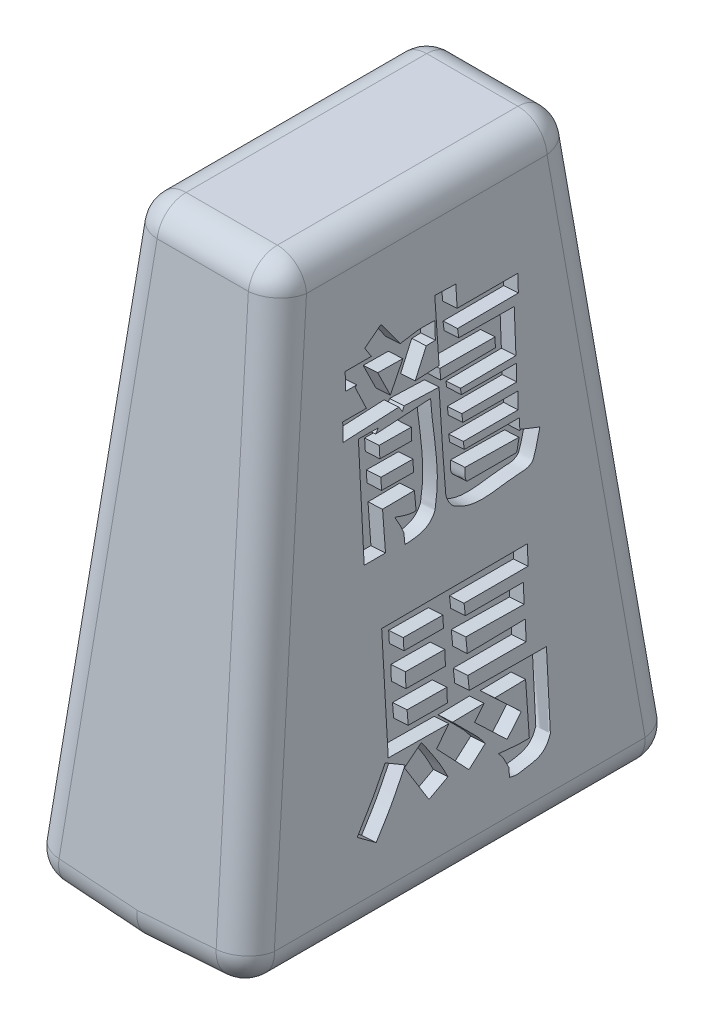
SolidWorks part; units mm, degrees
ref_plane "Płaszczyzna przednia" through (0, 0, 0) normal (0, 0, 1) x (1, 0, 0)
ref_plane "Płaszczyzna górna" through (0, 0, 0) normal (0, 1, 0) x (1, 0, 0)
ref_plane "Płaszczyzna prawa" through (0, 0, 0) normal (1, 0, 0) x (0, 0, -1)
sketch "Szkic1" plane through (0, 0, 0) normal (0, 0, 1) x (1, 0, 0)
  line L0 (0, 0) -> (0, 40)
  line L1 (3.1225, 40) -> (-3.1225, 40)
  line L2 (-5.1185, 38.1262) -> (-7.3738, 2.4704)
  line L3 (-5.504, 0.3481) -> (0, 0)
  line L4 (5.504, 0.3481) -> (0, 0)
  line L5 (5.1185, 38.1262) -> (7.3738, 2.4704)
  arc A0 (-3.1225, 40) -> (-5.1185, 38.1262) centre (-3.1225, 38) ccw
  arc A1 (-7.3738, 2.4704) -> (-5.504, 0.3481) centre (-5.3777, 2.3441) ccw
  arc A2 (7.3738, 2.4704) -> (5.504, 0.3481) centre (5.3777, 2.3441) cw
  arc A3 (3.1225, 40) -> (5.1185, 38.1262) centre (3.1225, 38) cw
  point P7 (-5, 40)
  point P10 (-7.5, 0.4744)
  point P17 (7.5, 0.4744)
  point P18 (5, 40)
  dimension "D5" = 2
  dimension "D1" = 40
  dimension "D2" = 90
  dimension "D3" = 5
  dimension "D4" = 7.5
extrude "Dodanie-wyciągnięcie1" add sketch "Szkic1" along normal blind 30 contours L2 A1 L3 L0 L1 A0 | A3 L1 L0 L4 A2 L5 region at (-3.1441, 18.7866, 0) region at (3.1441, 18.7866, 0)
ref_plane "Płaszczyzna1" through (5.1225, 0, 0) normal (1, 0, 0) x (0, 0, -1)
ref_plane "Płaszczyzna2" through (15.1225, 0, 0) normal (1, 0, 0) x (0, 0, -1)
sketch "Szkic7" plane through (15.1225, 0, 0) normal (1, 0, 0) x (0, 0, -1)
  line L0 (-25, 40) -> (-5, 40)
  line L1 (-30, 40) -> (0, 40) construction
  line L2 (-5, 40) -> (0, 0)
  line L3 (0, 0) -> (-30, 0)
  line L4 (-30, 0) -> (0, 0) construction
  line L5 (-15, 0) -> (-15, 40)
  line L6 (-25, 40) -> (-30, 0)
  line L8 (0, 0) -> (-30, 0)
  line L9 (0, 0) -> (0, 40)
  line L10 (0, 40) -> (-30, 40)
  line L11 (-30, 0) -> (-30, 40)
  dimension "D1" = 10
  dimension "D2" = 15
  dimension "D3" = 40
extrude "Wytnij-wyciągnięcie11" cut sketch "Szkic7" against normal through all and the other way through all contours L11 L6 L10 | L9 L10 L2 region at (15.1225, 26.6667, 28.3333) region at (15.1225, 26.6667, 1.6667)
fillet "Zaokrąglenie2" radius 2 18 edges at (0, 40, 5) (-4.4914, 39.4582, 4.9323) (-6.2461, 20.2983, 2.5373) (-6.8784, 1.022, 0.1278) (-2.752, 0.1741, 0.0218) (2.752, 0.1741, 0.0218) (6.8784, 1.022, 0.1278) (6.2461, 20.2983, 2.5373) (4.4914, 39.4582, 4.9323) (4.4914, 39.4582, 25.0677) (6.2461, 20.2983, 27.4627) (6.8784, 1.022, 29.8722) (2.752, 0.1741, 29.9782) (-2.752, 0.1741, 29.9782) (-6.8784, 1.022, 29.8722) (-6.2461, 20.2983, 27.4627) (-4.4914, 39.4582, 25.0677) (0, 40, 25)
sketch "Szkic8" plane through (-7.5, 0.4744, 0) normal (-0.998, 0.0631, 0) x (0, 0, 1)
  line L0 (200, 600) -> (1000, 600) construction
  line L1 (13.3902, 35.449) -> (15.0102, 34.657)
  line L2 (15.0102, 34.657) -> (14.6502, 33.937)
  line L3 (14.6502, 33.937) -> (18.6462, 33.865)
  line L4 (18.6462, 33.865) -> (18.7542, 32.533)
  line L5 (17.7462, 31.633) -> (20.8062, 31.561)
  line L6 (20.8062, 31.561) -> (20.7342, 22.921)
  line L7 (17.3862, 23.641) -> (19.2222, 23.497)
  line L8 (19.2222, 23.497) -> (19.1862, 25.621)
  line L9 (19.1862, 25.621) -> (16.7742, 25.549)
  line L10 (16.7742, 25.549) -> (16.7742, 22.669)
  line L11 (16.7742, 22.669) -> (15.1542, 22.741)
  line L12 (15.1542, 22.741) -> (15.1182, 25.621)
  line L13 (15.1182, 25.621) -> (13.0302, 25.549)
  line L14 (13.7502, 32.605) -> (16.4142, 32.569)
  line L15 (13.1022, 31.669) -> (13.7502, 32.605)
  line L16 (13.1022, 30.265) -> (15.1902, 30.229)
  line L17 (15.1902, 30.229) -> (15.1542, 29.437)
  line L18 (15.1542, 29.437) -> (13.1022, 29.473)
  line L19 (13.1022, 29.473) -> (13.1022, 30.265)
  line L20 (16.7742, 30.265) -> (19.2582, 30.229)
  line L21 (19.2582, 30.229) -> (19.2222, 29.437)
  line L22 (19.2222, 29.437) -> (16.7742, 29.473)
  line L23 (16.7742, 29.473) -> (16.7742, 30.265)
  line L24 (13.1022, 28.069) -> (15.1902, 28.033)
  line L25 (15.1902, 28.033) -> (15.1542, 26.989)
  line L26 (15.1542, 26.989) -> (13.1022, 27.025)
  line L27 (13.1022, 27.025) -> (13.1022, 28.069)
  line L28 (16.7742, 28.069) -> (19.2582, 28.033)
  line L29 (19.2582, 28.033) -> (19.2222, 26.989)
  line L30 (19.2222, 26.989) -> (16.7742, 27.025)
  line L31 (16.7742, 27.025) -> (16.7742, 28.069)
  line L32 (12.6702, 17.953) -> (14.2542, 17.233)
  line L33 (21.6342, 16.981) -> (21.9222, 16.945)
  line L34 (21.9222, 16.945) -> (21.8862, 15.505)
  line L35 (21.8862, 15.505) -> (15.0102, 15.541)
  line L36 (15.0102, 15.541) -> (15.0102, 16.981)
  line L37 (14.1822, 13.309) -> (22.7142, 13.273)
  line L38 (22.7142, 13.273) -> (22.6782, 11.833)
  line L39 (22.6782, 11.833) -> (19.8342, 11.833)
  line L40 (18.2142, 6.217) -> (18.2142, 11.869)
  line L41 (18.2142, 11.869) -> (14.1822, 11.869)
  line L42 (14.1822, 11.869) -> (14.1822, 13.309)
  line L43 (13.1022, 14.857) -> (14.6502, 14.065)
  line L44 (12.9942, 4.525) -> (12.9582, 4.381)
  line L45 (12.9582, 4.381) -> (11.1942, 4.417)
  line L46 (11.2302, 10.033) -> (9.9342, 8.845)
  line L47 (15.0102, 16.981) -> (21.6342, 16.981)
  line L48 (12.9942, 4.525) -> (12.9582, 11.8394)
  spline S0 degree 3 poles (18.7542, 32.533) (18.5862, 32.461) (18.3865, 32.4387) (18.2502, 32.317) (18.0389, 32.1284) (17.9142, 31.861) (17.7462, 31.633) knots 0 0 0 0 1 1 1 2 2 2 2
  spline S1 degree 3 poles (20.7342, 22.921) (20.7222, 22.897) (20.7133, 22.8711) (20.6982, 22.849) (20.5572, 22.6429) (20.4639, 22.3895) (20.2662, 22.237) (20.0279, 22.0532) (19.7331, 21.9369) (19.4382, 21.877) (18.9547, 21.7788) (18.4542, 21.805) (17.9622, 21.769) knots 0 0 0 0 1 1 1 2 2 2 3 3 3 4 4 4 4
  spline S2 degree 3 poles (17.9622, 21.769) (17.9262, 22.105) (17.9536, 22.454) (17.8542, 22.777) (17.7579, 23.09) (17.5422, 23.353) (17.3862, 23.641) knots 0 0 0 0 1 1 1 2 2 2 2
  spline S3 degree 3 poles (13.0302, 25.549) (12.9222, 25.141) (12.876, 24.7114) (12.7062, 24.325) (12.524, 23.9104) (12.2749, 23.5218) (11.9862, 23.173) (11.6938, 22.8197) (11.3442, 22.5132) (10.9782, 22.237) (10.7037, 22.0299) (10.3782, 21.901) (10.0782, 21.733) knots 0 0 0 0 1 1 1 2 2 2 3 3 3 4 4 4 4
  spline S4 degree 3 poles (10.0782, 21.733) (9.9342, 21.937) (9.8325, 22.1788) (9.6462, 22.345) (8.5139, 23.3549) (8.9213, 22.5708) (8.7102, 22.993) knots 0 0 0 0 1 1 1 2 2 2 2
  spline S5 degree 3 poles (8.7102, 22.993) (9.1782, 23.209) (9.6811, 23.3616) (10.1142, 23.641) (10.4351, 23.848) (10.7219, 24.121) (10.9422, 24.433) (11.1621, 24.7446) (11.3275, 25.1047) (11.4102, 25.477) (11.5224, 25.9819) (11.514, 26.5078) (11.5182, 27.025) (11.526, 27.9853) (11.4702, 28.945) (11.4462, 29.905) knots 0 0 0 0 1 1 1 2 2 2 3 3 3 4 4 4 5 5 5 5
  spline S6 degree 3 poles (11.4462, 29.905) (10.0065, 28.7684) (10.6122, 29.0538) (9.8262, 28.717) knots 0 0 0 0 1 1 1 1
  spline S7 degree 3 poles (9.8262, 28.717) (9.5982, 28.981) (9.3924, 29.2659) (9.1422, 29.509) (8.97, 29.6762) (8.7582, 29.797) (8.5662, 29.941) knots 0 0 0 0 1 1 1 2 2 2 2
  spline S8 degree 3 poles (8.5662, 29.941) (9.1782, 30.373) (9.8224, 30.7626) (10.4022, 31.237) (10.8816, 31.6293) (11.3388, 32.0561) (11.7342, 32.533) (12.4476, 33.3936) (12.9001, 34.4443) (13.3902, 35.449) knots 0 0 0 0 1 1 1 2 2 2 3 3 3 3
  spline S9 degree 3 poles (16.4142, 32.569) (16.271, 32.3542) (16.105, 32.1612) (15.9462, 31.957) (15.899, 31.8963) (15.8532, 31.8344) (15.8022, 31.777) (15.7571, 31.7263) (15.726, 31.6357) (15.6582, 31.633) (14.8068, 31.5989) (13.9542, 31.657) (13.1022, 31.669) knots 0 0 0 0 1 1 1 2 2 2 3 3 3 4 4 4 4
  spline S10 degree 3 poles (14.2542, 17.233) (14.107, 16.9386) (13.9054, 16.6727) (13.7142, 16.405) (12.9827, 15.3809) (12.1186, 14.48) (11.1222, 13.705) (10.7619, 13.4248) (10.4022, 13.1393) (10.0062, 12.913) knots 0 0 0 0 1 1 1 2 2 2 3 3 3 3
  spline S11 degree 3 poles (10.0062, 12.913) (9.7945, 13.2306) (9.4848, 13.4977) (9.1422, 13.669) (8.6933, 13.8934) (8.8531, 13.7421) (8.7102, 13.885) knots 0 0 0 0 1 1 1 2 2 2 2
  spline S12 degree 3 poles (8.7102, 13.885) (8.9097, 14.0845) (9.1639, 14.2278) (9.3942, 14.389) (9.7136, 14.6126) (10.0507, 14.8738) (10.3302, 15.145) (10.6712, 15.4759) (11.0072, 15.812) (11.3382, 16.153) (11.5397, 16.3606) (11.701, 16.6092) (11.8782, 16.837) (12.1581, 17.1969) (12.4286, 17.5664) (12.6702, 17.953) knots 0 0 0 0 1 1 1 2 2 2 3 3 3 4 4 4 5 5 5 5
  spline S14 degree 3 poles (19.8342, 11.833) (19.8222, 9.829) (19.822, 7.8249) (19.7982, 5.821) (19.798, 5.804) (19.7675, 5.8011) (19.7622, 5.785) (19.7309, 5.6911) (19.7215, 5.5909) (19.6902, 5.497) (19.6698, 5.4359) (19.5918, 5.3381) (19.5462, 5.281) (19.4305, 5.1364) (19.3192, 4.9751) (19.1502, 4.885) (19.0222, 4.8168) (18.8917, 4.7508) (18.7542, 4.705) (18.5664, 4.6424) (18.3731, 4.5954) (18.1782, 4.561) (17.6688, 4.4711) (17.147, 4.4737) (16.6302, 4.453) knots 0 0 0 0 1 1 1 2 2 2 3 3 3 4 4 4 5 5 5 6 6 6 7 7 7 8 8 8 8
  spline S15 degree 3 poles (16.6302, 4.453) (16.6302, 4.669) (16.6415, 4.8853) (16.6302, 5.101) (16.6293, 5.1179) (16.5995, 5.1209) (16.5942, 5.137) (16.5629, 5.2309) (16.5535, 5.3311) (16.5222, 5.425) (16.5168, 5.4411) (16.4944, 5.4462) (16.4862, 5.461) (16.4341, 5.5548) (16.3943, 5.6552) (16.3422, 5.749) (16.2396, 5.9336) (16.0439, 6.1285) (15.9102, 6.289) knots 0 0 0 0 1 1 1 2 2 2 3 3 3 4 4 4 5 5 5 6 6 6 6
  spline S16 degree 3 poles (15.9102, 6.289) (15.9222, 6.301) (15.9292, 6.3259) (15.9462, 6.325) (16.7018, 6.2822) (17.4604, 6.1485) (18.2142, 6.217) knots 0 0 0 0 1 1 1 2 2 2 2
  spline S17 degree 3 poles (14.6502, 14.065) (14.2608, 13.4809) (13.8644, 12.9208) (13.4262, 12.373) (13.3091, 12.2266) (13.1862, 12.085) (13.0662, 11.941) (13.017, 11.882) (12.9233, 11.8378) (12.9222, 11.761) (12.8186, 4.6837) (11.2621, 6.2571) (12.9942, 4.525) knots 0 0 0 0 1 1 1 2 2 2 3 3 3 4 4 4 4
  spline S18 degree 3 poles (11.1942, 4.417) (11.2182, 5.749) (11.2576, 7.0808) (11.2662, 8.413) (11.2696, 8.9531) (11.2422, 9.493) (11.2302, 10.033) knots 0 0 0 0 1 1 1 2 2 2 2
  spline S19 degree 3 poles (9.9342, 8.845) (9.8142, 8.953) (9.7016, 9.0699) (9.5742, 9.169) (9.2592, 9.414) (8.8543, 9.5489) (8.4942, 9.709) knots 0 0 0 0 1 1 1 2 2 2 2
  spline S20 degree 3 poles (8.4942, 9.709) (8.8719, 10.0867) (9.2988, 10.4157) (9.6822, 10.789) (10.5868, 11.6698) (11.4107, 12.5896) (12.1662, 13.597) (12.3822, 13.885) (12.5982, 14.173) (12.8142, 14.461) (12.9117, 14.591) (13.0295, 14.7116) (13.1022, 14.857) knots 0 0 0 0 1 1 1 2 2 2 3 3 3 4 4 4 4
extrude "Wytnij-wyciągnięcie12" cut sketch "Szkic8" against normal blind 1 contours S8 S7 S6 S5 S4 S3 L13 L12 L11 L10 L9 L8 L7 S2 S1 L6 L5 S0 L4 L3 L2 L1 L18 L19 L16 L17 L22 L23 L20 L21 L26 L27 L24 L25 L30 L31 L28 L29 L14 S9 L15 | L47 L36 L35 L34 L33 | S12 S11 S10 L32 | S20 S19 L46 S18 L45 L44 S17 L43 | L48 S17 | S16 S15 S14 L39 L38 L37 L42 L41 L40 region at (-5.7076, 28.812, 15.4989) region at (-6.5262, 15.8703, 11.5989) region at (-6.4741, 16.6942, 18.4699) region at (-6.8723, 10.3977, 18.5309) region at (-6.8488, 10.7708, 11.7119) region at (-6.9835, 8.6399, 12.9026)
sketch "Szkic9" plane through (7.5, 0.4744, 0) normal (0.998, 0.0631, 0) x (0, 0, -1)
  line L0 (341.3333, 1024) -> (1706.6667, 1024) construction
  line L1 (341.3333, 1024) -> (1706.6667, 1024) construction
  line L2 (-20.3008, 27.9246) -> (-18.9408, 27.9046)
  line L3 (-18.9408, 27.9046) -> (-19.1408, 27.6446)
  line L4 (-19.1408, 27.6446) -> (-15.3608, 27.8646)
  line L5 (-18.1408, 22.3446) -> (-18.1208, 22.3646)
  line L6 (-16.7208, 22.0646) -> (-16.7608, 23.2446)
  line L7 (-16.7608, 23.2446) -> (-18.9408, 23.2246)
  line L8 (-18.9408, 23.2246) -> (-18.9008, 20.6846)
  line L9 (-18.9008, 20.6846) -> (-20.2808, 20.6846)
  line L10 (-20.2808, 20.6846) -> (-20.3608, 20.7046)
  line L11 (-20.3608, 20.7046) -> (-20.3008, 27.9246)
  line L12 (-18.9408, 26.9046) -> (-16.7408, 26.8846)
  line L13 (-16.7408, 26.8846) -> (-16.7608, 26.1046)
  line L14 (-16.7608, 26.1046) -> (-18.9408, 26.1246)
  line L15 (-18.9408, 26.1246) -> (-18.9408, 26.9046)
  line L16 (-18.9408, 25.0646) -> (-16.7408, 25.0446)
  line L17 (-16.7408, 25.0446) -> (-16.7608, 24.2846)
  line L18 (-16.7608, 24.2846) -> (-18.9408, 24.3046)
  line L19 (-18.9408, 24.3046) -> (-18.9408, 25.0646)
  line L20 (-14.8008, 32.0846) -> (-14.8408, 30.9646)
  line L21 (-14.8408, 30.9646) -> (-15.4608, 30.9446)
  line L22 (-15.4608, 30.9446) -> (-16.3208, 29.3446)
  line L23 (-16.3208, 29.3446) -> (-14.6808, 29.4246)
  line L24 (-14.6808, 29.4246) -> (-14.7208, 33.4846)
  line L25 (-14.7208, 33.4846) -> (-13.2808, 33.4446)
  line L26 (-13.2808, 33.4446) -> (-13.2808, 32.0446)
  line L27 (-13.2808, 32.0446) -> (-9.1208, 32.0446)
  line L28 (-9.1208, 32.0446) -> (-9.1608, 30.9246)
  line L29 (-9.1608, 30.9246) -> (-13.3208, 30.9046)
  line L30 (-13.3208, 30.9046) -> (-13.2808, 30.3446)
  line L31 (-13.2808, 30.3446) -> (-9.4808, 30.3046)
  line L32 (-9.4808, 30.3046) -> (-9.5408, 27.5046)
  line L33 (-9.5408, 27.5046) -> (-13.3408, 27.4646)
  line L34 (-13.3408, 27.4646) -> (-13.3008, 27.0846)
  line L35 (-13.3008, 27.0846) -> (-9.5408, 27.0646)
  line L36 (-9.5408, 27.0646) -> (-9.5808, 26.0046)
  line L37 (-9.5808, 26.0046) -> (-13.3408, 26.0046)
  line L38 (-13.3408, 26.0046) -> (-13.3008, 25.4846)
  line L39 (-13.3008, 25.4846) -> (-9.5408, 25.4646)
  line L40 (-9.5408, 25.4646) -> (-9.5808, 24.4046)
  line L41 (-9.5808, 24.4046) -> (-13.3408, 24.4046)
  line L42 (-13.3408, 24.4046) -> (-13.3008, 23.9246)
  line L43 (-13.3008, 23.9246) -> (-9.5408, 23.9246)
  line L44 (-9.5408, 23.9246) -> (-9.5408, 23.1846)
  line L45 (-9.5408, 23.1846) -> (-9.4608, 23.2246)
  line L46 (-9.4608, 23.2246) -> (-8.2008, 22.7446)
  line L47 (-14.7608, 28.2246) -> (-17.1408, 28.3046)
  line L48 (-17.1408, 28.3046) -> (-17.2808, 28.0446)
  line L49 (-17.2808, 28.0446) -> (-17.5008, 28.4046)
  line L50 (-17.5008, 28.4046) -> (-21.3208, 28.2246)
  line L51 (-21.3208, 28.2246) -> (-21.2808, 29.3846)
  line L52 (-21.2808, 29.3846) -> (-19.6608, 29.3846)
  line L53 (-19.6608, 29.3846) -> (-20.3408, 30.9246)
  line L54 (-20.3408, 30.9246) -> (-20.2208, 31.0046)
  line L55 (-20.2208, 31.0046) -> (-20.9808, 31.0046)
  line L56 (-20.9808, 31.0046) -> (-20.9408, 32.1246)
  line L57 (-20.9408, 32.1246) -> (-19.1408, 32.1246)
  line L58 (-19.1408, 32.1246) -> (-19.5608, 32.7846)
  line L59 (-19.5608, 32.7846) -> (-18.4208, 33.5846)
  line L60 (-18.7808, 31.0046) -> (-17.0608, 30.9846)
  line L61 (-17.0608, 30.9846) -> (-18.0208, 29.3446)
  line L62 (-18.0208, 29.3446) -> (-18.7808, 31.0046)
  line L63 (-14.6408, 29.2446) -> (-10.8608, 29.2246)
  line L64 (-10.8608, 29.2246) -> (-10.8808, 28.6046)
  line L65 (-10.8808, 28.6046) -> (-14.6208, 28.5646)
  line L66 (-14.6208, 28.5646) -> (-14.6408, 29.2446)
  line L67 (-13.3208, 22.9046) -> (-9.6208, 22.8446)
  line L68 (-14.8008, 32.0846) -> (-14.8408, 30.9646)
  line L69 (-14.8408, 30.9646) -> (-15.4608, 30.9446)
  line L70 (-15.4608, 30.9446) -> (-16.3208, 29.3446)
  line L71 (-16.3208, 29.3446) -> (-14.6808, 29.4246)
  line L72 (-14.6808, 29.4246) -> (-14.7208, 33.4846)
  line L73 (-14.7208, 33.4846) -> (-13.2808, 33.4446)
  line L74 (-13.2808, 33.4446) -> (-13.2808, 32.0446)
  line L75 (-13.2808, 32.0446) -> (-9.1208, 32.0446)
  line L76 (-9.1208, 32.0446) -> (-9.1608, 30.9246)
  line L77 (-9.1608, 30.9246) -> (-13.3208, 30.9046)
  line L78 (-13.3208, 30.9046) -> (-13.2808, 30.3446)
  line L79 (-13.2808, 30.3446) -> (-9.4808, 30.3046)
  line L80 (-9.4808, 30.3046) -> (-9.5408, 27.5046)
  line L81 (-9.5408, 27.5046) -> (-13.3408, 27.4646)
  line L82 (-13.3408, 27.4646) -> (-13.3008, 27.0846)
  line L83 (-13.3008, 27.0846) -> (-9.5408, 27.0646)
  line L84 (-9.5408, 27.0646) -> (-9.5808, 26.0046)
  line L85 (-9.5808, 26.0046) -> (-13.3408, 26.0046)
  line L86 (-13.3408, 26.0046) -> (-13.3008, 25.4846)
  line L87 (-13.3008, 25.4846) -> (-9.5408, 25.4646)
  line L88 (-9.5408, 25.4646) -> (-9.5808, 24.4046)
  line L89 (-9.5808, 24.4046) -> (-13.3408, 24.4046)
  line L90 (-13.3408, 24.4046) -> (-13.3008, 23.9246)
  line L91 (-13.3008, 23.9246) -> (-9.5408, 23.9246)
  line L92 (-9.5408, 23.9246) -> (-9.5408, 23.1846)
  line L93 (-9.5408, 23.1846) -> (-9.4608, 23.2246)
  line L94 (-9.4608, 23.2246) -> (-8.2008, 22.7446)
  line L95 (-14.7608, 28.2246) -> (-17.1408, 28.3046)
  line L96 (-17.1408, 28.3046) -> (-17.2808, 28.0446)
  line L97 (-17.2808, 28.0446) -> (-17.5008, 28.4046)
  line L98 (-17.5008, 28.4046) -> (-21.3208, 28.2246)
  line L99 (-21.3208, 28.2246) -> (-21.2808, 29.3846)
  line L100 (-21.2808, 29.3846) -> (-19.6608, 29.3846)
  line L101 (-19.6608, 29.3846) -> (-20.3408, 30.9246)
  line L102 (-20.3408, 30.9246) -> (-20.2208, 31.0046)
  line L103 (-20.2208, 31.0046) -> (-20.9808, 31.0046)
  line L104 (-20.9808, 31.0046) -> (-20.9408, 32.1246)
  line L105 (-20.9408, 32.1246) -> (-19.1408, 32.1246)
  line L106 (-19.1408, 32.1246) -> (-19.5608, 32.7846)
  line L107 (-19.5608, 32.7846) -> (-18.4208, 33.5846)
  line L108 (-18.7808, 31.0046) -> (-17.0608, 30.9846)
  line L109 (-17.0608, 30.9846) -> (-18.0208, 29.3446)
  line L110 (-18.0208, 29.3446) -> (-18.7808, 31.0046)
  line L111 (-14.6408, 29.2446) -> (-10.8608, 29.2246)
  line L112 (-10.8608, 29.2246) -> (-10.8808, 28.6046)
  line L113 (-10.8808, 28.6046) -> (-14.6208, 28.5646)
  line L114 (-14.6208, 28.5646) -> (-14.6408, 29.2446)
  line L115 (-13.3208, 22.9046) -> (-9.6208, 22.8446)
  line L116 (-9.5208, 16.6446) -> (-9.4408, 16.6046)
  line L117 (-9.4408, 16.6046) -> (-9.4808, 15.3446)
  line L118 (-9.4808, 15.3446) -> (-13.8608, 15.3446)
  line L119 (-13.8608, 15.3446) -> (-13.8208, 14.6046)
  line L120 (-13.8208, 14.6046) -> (-9.8408, 14.6046)
  line L121 (-9.8408, 14.6046) -> (-9.8808, 13.3446)
  line L122 (-9.8808, 13.3446) -> (-13.8608, 13.4046)
  line L123 (-13.8608, 13.4046) -> (-13.8208, 12.4246)
  line L124 (-13.8208, 12.4246) -> (-9.9208, 12.4846)
  line L125 (-9.9208, 12.4846) -> (-9.8408, 12.4446)
  line L126 (-9.8408, 12.4446) -> (-9.8808, 11.1846)
  line L127 (-9.8808, 11.1846) -> (-13.8608, 11.1846)
  line L128 (-13.8608, 11.1846) -> (-13.8208, 10.3046)
  line L129 (-13.8208, 10.3046) -> (-8.5408, 10.2646)
  line L130 (-10.0008, 5.7046) -> (-10.0408, 9.1046)
  line L131 (-10.0408, 9.1046) -> (-12.1608, 9.0646)
  line L132 (-12.1608, 9.0646) -> (-10.4408, 7.4446)
  line L133 (-10.4408, 7.4446) -> (-11.4808, 6.3446)
  line L134 (-11.4808, 6.3446) -> (-13.5808, 8.3446)
  line L135 (-13.5808, 8.3446) -> (-12.8808, 9.1046)
  line L136 (-12.8808, 9.1046) -> (-15.0408, 9.0646)
  line L137 (-12.9408, 6.8246) -> (-14.1208, 5.8846)
  line L138 (-14.1208, 5.8846) -> (-16.2008, 8.0846)
  line L139 (-16.2008, 8.0846) -> (-15.3008, 9.1046)
  line L140 (-15.3008, 9.1046) -> (-19.4408, 9.1446)
  line L141 (-19.4408, 9.1446) -> (-19.4208, 16.5846)
  line L142 (-19.4208, 16.5846) -> (-9.5208, 16.6246)
  line L143 (-9.5208, 16.6246) -> (-9.5208, 16.6446)
  line L144 (-18.0208, 15.3846) -> (-15.3008, 15.3646)
  line L145 (-15.3008, 15.3646) -> (-15.3208, 14.6046)
  line L146 (-15.3208, 14.6046) -> (-18.0208, 14.6246)
  line L147 (-18.0208, 14.6246) -> (-18.0208, 15.3846)
  line L148 (-18.0008, 13.4046) -> (-15.3008, 13.3846)
  line L149 (-15.3008, 13.3846) -> (-15.3208, 12.4246)
  line L150 (-15.3208, 12.4246) -> (-18.0208, 12.4446)
  line L151 (-18.0208, 12.4446) -> (-18.0008, 13.4046)
  line L152 (-18.0208, 11.2246) -> (-15.3008, 11.2046)
  line L153 (-15.3008, 11.2046) -> (-15.3208, 10.3046)
  line L154 (-15.3208, 10.3046) -> (-18.0008, 10.3246)
  line L155 (-18.0008, 10.3246) -> (-18.0208, 11.2246)
  line L156 (-19.6608, 8.9646) -> (-18.3408, 8.2046)
  line L157 (-20.5408, 4.8046) -> (-21.7808, 5.7046)
  line L158 (-15.5408, 6.1646) -> (-16.8808, 5.5046)
  line L159 (-16.8808, 5.5046) -> (-18.4008, 8.0646)
  line L160 (-18.4008, 8.0646) -> (-17.2008, 8.9246)
  line L161 (-9.5208, 16.6446) -> (-9.4408, 16.6046)
  line L162 (-9.4408, 16.6046) -> (-9.4808, 15.3446)
  line L163 (-9.4808, 15.3446) -> (-13.8608, 15.3446)
  line L164 (-13.8608, 15.3446) -> (-13.8208, 14.6046)
  line L165 (-13.8208, 14.6046) -> (-9.8408, 14.6046)
  line L166 (-9.8408, 14.6046) -> (-9.8808, 13.3446)
  line L167 (-9.8808, 13.3446) -> (-13.8608, 13.4046)
  line L168 (-13.8608, 13.4046) -> (-13.8208, 12.4246)
  line L169 (-13.8208, 12.4246) -> (-9.9208, 12.4846)
  line L170 (-9.9208, 12.4846) -> (-9.8408, 12.4446)
  line L171 (-9.8408, 12.4446) -> (-9.8808, 11.1846)
  line L172 (-9.8808, 11.1846) -> (-13.8608, 11.1846)
  line L173 (-13.8608, 11.1846) -> (-13.8208, 10.3046)
  line L174 (-13.8208, 10.3046) -> (-8.5408, 10.2646)
  line L175 (-10.0008, 5.7046) -> (-10.0408, 9.1046)
  line L176 (-10.0408, 9.1046) -> (-12.1608, 9.0646)
  line L177 (-12.1608, 9.0646) -> (-10.4408, 7.4446)
  line L178 (-10.4408, 7.4446) -> (-11.4808, 6.3446)
  line L179 (-11.4808, 6.3446) -> (-13.5808, 8.3446)
  line L180 (-13.5808, 8.3446) -> (-12.8808, 9.1046)
  line L181 (-12.8808, 9.1046) -> (-15.0408, 9.0646)
  line L182 (-12.9408, 6.8246) -> (-14.1208, 5.8846)
  line L183 (-14.1208, 5.8846) -> (-16.2008, 8.0846)
  line L184 (-16.2008, 8.0846) -> (-15.3008, 9.1046)
  line L185 (-15.3008, 9.1046) -> (-19.4408, 9.1446)
  line L186 (-19.4408, 9.1446) -> (-19.4208, 16.5846)
  line L187 (-19.4208, 16.5846) -> (-9.5208, 16.6246)
  line L188 (-9.5208, 16.6246) -> (-9.5208, 16.6446)
  line L189 (-18.0208, 15.3846) -> (-15.3008, 15.3646)
  line L190 (-15.3008, 15.3646) -> (-15.3208, 14.6046)
  line L191 (-15.3208, 14.6046) -> (-18.0208, 14.6246)
  line L192 (-18.0208, 14.6246) -> (-18.0208, 15.3846)
  line L193 (-18.0008, 13.4046) -> (-15.3008, 13.3846)
  line L194 (-15.3008, 13.3846) -> (-15.3208, 12.4246)
  line L195 (-15.3208, 12.4246) -> (-18.0208, 12.4446)
  line L196 (-18.0208, 12.4446) -> (-18.0008, 13.4046)
  line L197 (-18.0208, 11.2246) -> (-15.3008, 11.2046)
  line L198 (-15.3008, 11.2046) -> (-15.3208, 10.3046)
  line L199 (-15.3208, 10.3046) -> (-18.0008, 10.3246)
  line L200 (-18.0008, 10.3246) -> (-18.0208, 11.2246)
  line L201 (-9.5208, 16.6446) -> (-9.4408, 16.6046)
  line L202 (-9.4408, 16.6046) -> (-9.4808, 15.3446)
  line L203 (-9.4808, 15.3446) -> (-13.8608, 15.3446)
  line L204 (-13.8608, 15.3446) -> (-13.8208, 14.6046)
  line L205 (-13.8208, 14.6046) -> (-9.8408, 14.6046)
  line L206 (-9.8408, 14.6046) -> (-9.8808, 13.3446)
  line L207 (-9.8808, 13.3446) -> (-13.8608, 13.4046)
  line L208 (-13.8608, 13.4046) -> (-13.8208, 12.4246)
  line L209 (-13.8208, 12.4246) -> (-9.9208, 12.4846)
  line L210 (-9.9208, 12.4846) -> (-9.8408, 12.4446)
  line L211 (-9.8408, 12.4446) -> (-9.8808, 11.1846)
  line L212 (-9.8808, 11.1846) -> (-13.8608, 11.1846)
  line L213 (-13.8608, 11.1846) -> (-13.8208, 10.3046)
  line L214 (-13.8208, 10.3046) -> (-8.5408, 10.2646)
  line L215 (-10.0008, 5.7046) -> (-10.0408, 9.1046)
  line L216 (-10.0408, 9.1046) -> (-12.1608, 9.0646)
  line L217 (-12.1608, 9.0646) -> (-10.4408, 7.4446)
  line L218 (-10.4408, 7.4446) -> (-11.4808, 6.3446)
  line L219 (-11.4808, 6.3446) -> (-13.5808, 8.3446)
  line L220 (-13.5808, 8.3446) -> (-12.8808, 9.1046)
  line L221 (-12.8808, 9.1046) -> (-15.0408, 9.0646)
  line L222 (-12.9408, 6.8246) -> (-14.1208, 5.8846)
  line L223 (-14.1208, 5.8846) -> (-16.2008, 8.0846)
  line L224 (-16.2008, 8.0846) -> (-15.3008, 9.1046)
  line L225 (-15.3008, 9.1046) -> (-19.4408, 9.1446)
  line L226 (-19.4408, 9.1446) -> (-19.4208, 16.5846)
  line L227 (-19.4208, 16.5846) -> (-9.5208, 16.6246)
  line L228 (-9.5208, 16.6246) -> (-9.5208, 16.6446)
  line L229 (-18.0208, 15.3846) -> (-15.3008, 15.3646)
  line L230 (-15.3008, 15.3646) -> (-15.3208, 14.6046)
  line L231 (-15.3208, 14.6046) -> (-18.0208, 14.6246)
  line L232 (-18.0208, 14.6246) -> (-18.0208, 15.3846)
  line L233 (-18.0008, 13.4046) -> (-15.3008, 13.3846)
  line L234 (-15.3008, 13.3846) -> (-15.3208, 12.4246)
  line L235 (-15.3208, 12.4246) -> (-18.0208, 12.4446)
  line L236 (-18.0208, 12.4446) -> (-18.0008, 13.4046)
  line L237 (-18.0208, 11.2246) -> (-15.3008, 11.2046)
  line L238 (-15.3008, 11.2046) -> (-15.3208, 10.3046)
  line L239 (-15.3208, 10.3046) -> (-18.0008, 10.3246)
  line L240 (-18.0008, 10.3246) -> (-18.0208, 11.2246)
  spline S0 degree 3 poles (-15.3608, 27.8646) (-15.3675, 25.8379) (-14.9093, 23.7508) (-15.4008, 21.7846) (-15.4255, 21.6857) (-15.4361, 21.5836) (-15.4608, 21.4846) (-15.4747, 21.4291) (-15.5283, 21.3588) (-15.5608, 21.3046) (-15.7784, 20.942) (-16.1274, 20.7452) (-16.5408, 20.6446) (-16.8799, 20.5622) (-17.2326, 20.5479) (-17.5808, 20.5246) knots 0 0 0 0 1 1 1 2 2 2 3 3 3 4 4 4 5 5 5 5
  spline S1 degree 3 poles (-17.5808, 20.5246) (-17.5875, 20.738) (-17.5879, 20.9516) (-17.6008, 21.1646) (-17.6045, 21.2251) (-17.6562, 21.3371) (-17.6808, 21.4046) (-17.8046, 21.7451) (-17.9832, 22.0294) (-18.1408, 22.3446) knots 0 0 0 0 1 1 1 2 2 2 3 3 3 3
  spline S2 degree 3 poles (-18.1208, 22.3646) (-17.6682, 22.2315) (-17.1973, 22.0213) (-16.7208, 22.0646) knots 0 0 0 0 1 1 1 1
  spline S3 degree 3 poles (-18.4208, 33.5846) (-18.3941, 33.5713) (-18.3585, 33.5686) (-18.3408, 33.5446) (-17.9432, 33.0059) (-17.5675, 32.4513) (-17.1808, 31.9046) knots 0 0 0 0 1 1 1 2 2 2 2
  spline S4 degree 3 poles (-17.1808, 31.9046) (-16.7675, 31.9646) (-16.3573, 32.0531) (-15.9408, 32.0846) (-15.5619, 32.1133) (-15.1808, 32.0846) (-14.8008, 32.0846) knots 0 0 0 0 1 1 1 2 2 2 2
  spline S5 degree 3 poles (-8.2008, 22.7446) (-8.3808, 22.2246) (-8.5102, 21.6843) (-8.7408, 21.1846) (-8.7963, 21.0645) (-8.9212, 20.9813) (-9.0408, 20.9246) (-9.1826, 20.8575) (-9.3439, 20.8267) (-9.5008, 20.8246) (-10.9142, 20.8064) (-12.486, 20.234) (-13.7408, 20.8846) (-13.9076, 20.9711) (-14.0999, 21.0205) (-14.2408, 21.1446) (-14.3879, 21.2742) (-14.5015, 21.4453) (-14.5808, 21.6246) (-14.658, 21.7992) (-14.6956, 21.9938) (-14.7008, 22.1846) (-14.7557, 24.1973) (-14.7408, 26.2113) (-14.7608, 28.2246) knots 0 0 0 0 1 1 1 2 2 2 3 3 3 4 4 4 5 5 5 6 6 6 7 7 7 8 8 8 8
  spline S6 degree 3 poles (-9.6208, 22.8446) (-9.6627, 22.6701) (-9.7092, 22.4966) (-9.7608, 22.3246) (-9.8006, 22.1921) (-9.7803, 22.0668) (-9.9608, 22.0646) (-11.0541, 22.0518) (-12.1475, 22.0646) (-13.2408, 22.0646) knots 0 0 0 0 1 1 1 2 2 2 3 3 3 3
  spline S7 degree 3 poles (-13.2408, 22.0646) (-13.4066, 22.2856) (-13.3298, 22.6698) (-13.3208, 22.9046) knots 0 0 0 0 1 1 1 1
  spline S8 degree 3 poles (-18.4208, 33.5846) (-18.3941, 33.5713) (-18.3585, 33.5686) (-18.3408, 33.5446) (-17.9432, 33.0059) (-17.5675, 32.4513) (-17.1808, 31.9046) knots 0 0 0 0 1 1 1 2 2 2 2
  spline S9 degree 3 poles (-17.1808, 31.9046) (-16.7675, 31.9646) (-16.3573, 32.0531) (-15.9408, 32.0846) (-15.5619, 32.1133) (-15.1808, 32.0846) (-14.8008, 32.0846) knots 0 0 0 0 1 1 1 2 2 2 2
  spline S10 degree 3 poles (-8.2008, 22.7446) (-8.3808, 22.2246) (-8.5102, 21.6843) (-8.7408, 21.1846) (-8.7963, 21.0645) (-8.9212, 20.9813) (-9.0408, 20.9246) (-9.1826, 20.8575) (-9.3439, 20.8267) (-9.5008, 20.8246) (-10.9142, 20.8064) (-12.486, 20.234) (-13.7408, 20.8846) (-13.9076, 20.9711) (-14.0999, 21.0205) (-14.2408, 21.1446) (-14.3879, 21.2742) (-14.5015, 21.4453) (-14.5808, 21.6246) (-14.658, 21.7992) (-14.6956, 21.9938) (-14.7008, 22.1846) (-14.7557, 24.1973) (-14.7408, 26.2113) (-14.7608, 28.2246) knots 0 0 0 0 1 1 1 2 2 2 3 3 3 4 4 4 5 5 5 6 6 6 7 7 7 8 8 8 8
  spline S11 degree 3 poles (-9.6208, 22.8446) (-9.6627, 22.6701) (-9.7092, 22.4966) (-9.7608, 22.3246) (-9.8006, 22.1921) (-9.7803, 22.0668) (-9.9608, 22.0646) (-11.0541, 22.0518) (-12.1475, 22.0646) (-13.2408, 22.0646) knots 0 0 0 0 1 1 1 2 2 2 3 3 3 3
  spline S12 degree 3 poles (-13.2408, 22.0646) (-13.4066, 22.2856) (-13.3298, 22.6698) (-13.3208, 22.9046) knots 0 0 0 0 1 1 1 1
  spline S13 degree 3 poles (-8.5408, 10.2646) (-8.5541, 8.6046) (-8.561, 6.9446) (-8.5808, 5.2846) (-8.581, 5.2697) (-8.5935, 5.2576) (-8.6008, 5.2446) (-8.6869, 5.091) (-8.7484, 4.9202) (-8.8608, 4.7846) (-8.9785, 4.6427) (-9.1171, 4.5094) (-9.2808, 4.4246) (-9.498, 4.3122) (-9.7394, 4.2437) (-9.9808, 4.2046) (-11.0174, 4.0371) (-10.8906, 4.0306) (-11.4608, 4.1446) knots 0 0 0 0 1 1 1 2 2 2 3 3 3 4 4 4 5 5 5 6 6 6 6
  spline S14 degree 3 poles (-11.4608, 4.1446) (-11.4849, 4.891) (-11.3881, 4.5717) (-11.5008, 4.8046) (-11.5943, 4.9979) (-11.672, 5.1996) (-11.7808, 5.3846) (-11.8728, 5.541) (-11.9941, 5.678) (-12.1008, 5.8246) knots 0 0 0 0 1 1 1 2 2 2 3 3 3 3
  spline S15 degree 3 poles (-12.1008, 5.8246) (-11.402, 5.7678) (-10.701, 5.6678) (-10.0008, 5.7046) knots 0 0 0 0 1 1 1 1
  spline S16 degree 3 poles (-15.0408, 9.0646) (-14.5008, 8.518) (-13.9464, 7.9852) (-13.4208, 7.4246) (-13.2456, 7.2378) (-13.1008, 7.0246) (-12.9408, 6.8246) knots 0 0 0 0 1 1 1 2 2 2 2
  spline S17 degree 3 poles (-18.3408, 8.2046) (-18.7075, 7.5913) (-19.0526, 6.9646) (-19.4408, 6.3646) (-19.7865, 5.8304) (-20.1741, 5.3246) (-20.5408, 4.8046) knots 0 0 0 0 1 1 1 2 2 2 2
  spline S18 degree 3 poles (-21.7808, 5.7046) (-21.3675, 6.3046) (-20.938, 6.8938) (-20.5408, 7.5046) (-20.231, 7.981) (-19.9541, 8.478) (-19.6608, 8.9646) knots 0 0 0 0 1 1 1 2 2 2 2
  spline S19 degree 3 poles (-17.2008, 8.9246) (-17.1675, 8.8913) (-17.1266, 8.8641) (-17.1008, 8.8246) (-16.7461, 8.2832) (-16.3883, 7.743) (-16.0608, 7.1846) (-15.8677, 6.8554) (-15.7141, 6.5046) (-15.5408, 6.1646) knots 0 0 0 0 1 1 1 2 2 2 3 3 3 3
  spline S20 degree 3 poles (-8.5408, 10.2646) (-8.5541, 8.6046) (-8.561, 6.9446) (-8.5808, 5.2846) (-8.581, 5.2697) (-8.5935, 5.2576) (-8.6008, 5.2446) (-8.6869, 5.091) (-8.7484, 4.9202) (-8.8608, 4.7846) (-8.9785, 4.6427) (-9.1171, 4.5094) (-9.2808, 4.4246) (-9.498, 4.3122) (-9.7394, 4.2437) (-9.9808, 4.2046) (-11.0174, 4.0371) (-10.8906, 4.0306) (-11.4608, 4.1446) knots 0 0 0 0 1 1 1 2 2 2 3 3 3 4 4 4 5 5 5 6 6 6 6
  spline S21 degree 3 poles (-11.4608, 4.1446) (-11.4849, 4.891) (-11.3881, 4.5717) (-11.5008, 4.8046) (-11.5943, 4.9979) (-11.672, 5.1996) (-11.7808, 5.3846) (-11.8728, 5.541) (-11.9941, 5.678) (-12.1008, 5.8246) knots 0 0 0 0 1 1 1 2 2 2 3 3 3 3
  spline S22 degree 3 poles (-12.1008, 5.8246) (-11.402, 5.7678) (-10.701, 5.6678) (-10.0008, 5.7046) knots 0 0 0 0 1 1 1 1
  spline S23 degree 3 poles (-15.0408, 9.0646) (-14.5008, 8.518) (-13.9464, 7.9852) (-13.4208, 7.4246) (-13.2456, 7.2378) (-13.1008, 7.0246) (-12.9408, 6.8246) knots 0 0 0 0 1 1 1 2 2 2 2
  spline S24 degree 3 poles (-8.5408, 10.2646) (-8.5541, 8.6046) (-8.561, 6.9446) (-8.5808, 5.2846) (-8.581, 5.2697) (-8.5935, 5.2576) (-8.6008, 5.2446) (-8.6869, 5.091) (-8.7484, 4.9202) (-8.8608, 4.7846) (-8.9785, 4.6427) (-9.1171, 4.5094) (-9.2808, 4.4246) (-9.498, 4.3122) (-9.7394, 4.2437) (-9.9808, 4.2046) (-11.0174, 4.0371) (-10.8906, 4.0306) (-11.4608, 4.1446) knots 0 0 0 0 1 1 1 2 2 2 3 3 3 4 4 4 5 5 5 6 6 6 6
  spline S25 degree 3 poles (-11.4608, 4.1446) (-11.4849, 4.891) (-11.3881, 4.5717) (-11.5008, 4.8046) (-11.5943, 4.9979) (-11.672, 5.1996) (-11.7808, 5.3846) (-11.8728, 5.541) (-11.9941, 5.678) (-12.1008, 5.8246) knots 0 0 0 0 1 1 1 2 2 2 3 3 3 3
  spline S26 degree 3 poles (-12.1008, 5.8246) (-11.402, 5.7678) (-10.701, 5.6678) (-10.0008, 5.7046) knots 0 0 0 0 1 1 1 1
  spline S27 degree 3 poles (-15.0408, 9.0646) (-14.5008, 8.518) (-13.9464, 7.9852) (-13.4208, 7.4246) (-13.2456, 7.2378) (-13.1008, 7.0246) (-12.9408, 6.8246) knots 0 0 0 0 1 1 1 2 2 2 2
extrude "Wytnij-wyciągnięcie13" cut sketch "Szkic9" against normal blind 1 contours S2 L5 S1 S0 L4 L3 L2 L11 L10 L9 L8 L7 L6 L14 L15 L12 L13 L18 L19 L16 L17 | S5 L46 L45 L44 L43 L42 L41 L40 L39 L38 L37 L36 L35 L34 L33 L32 L31 L30 L29 L28 L27 L26 L25 L24 L23 L22 L21 L20 S4 S3 L59 L58 L57 L56 L55 L54 L53 L52 L51 L50 L49 L48 L47 L65 L66 L63 L64 L61 L62 | S16 L136 L135 L134 L133 L132 L131 L130 S15 S14 S13 L129 L128 L127 L126 L125 L124 L123 L122 L121 L120 L119 L118 L117 L116 L143 L142 L141 L140 L139 L138 L137 L146 L147 L144 L145 L150 L151 L148 L149 L154 L155 L152 L153 | S19 L160 L159 L158 | S18 L157 S17 L156 region at (5.7436, 28.2432, 19.6221) region at (5.7427, 28.2572, 13.7653) region at (6.7914, 11.6782, 13.9216) region at (7.0649, 7.353, 20.0461) region at (7.044, 7.6836, 16.9963)
